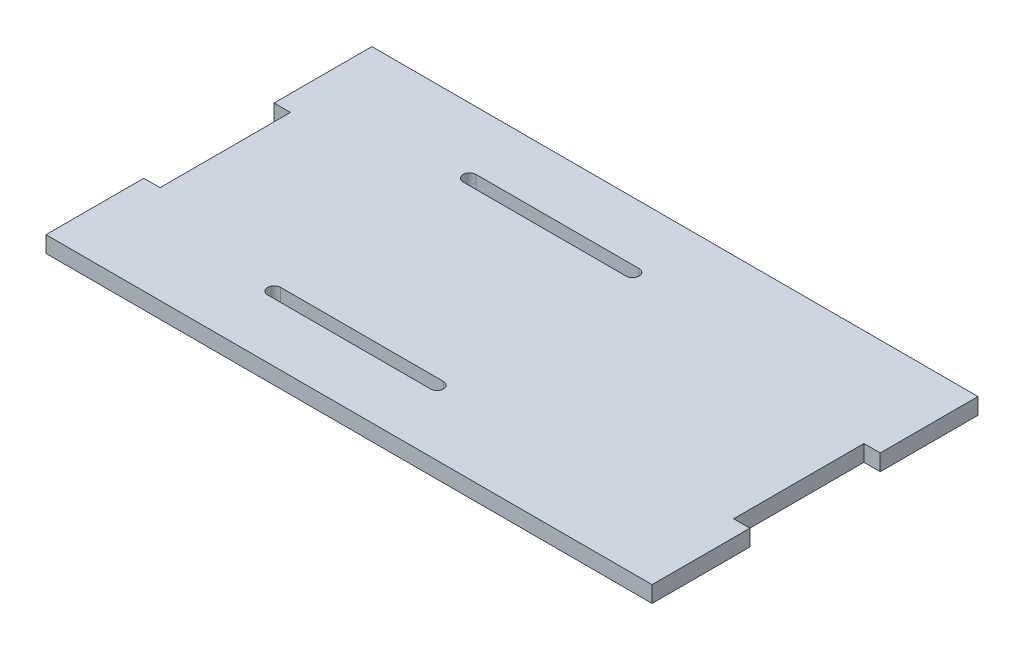
SolidWorks part; units mm, degrees
ref_plane "Front" through (0, 0, 0) normal (0, 0, 1) x (1, 0, 0)
ref_plane "Top" through (0, 0, 0) normal (0, 1, 0) x (1, 0, 0)
ref_plane "Right" through (0, 0, 0) normal (1, 0, 0) x (0, 0, -1)
sketch "Skizze1" plane through (0, 0, 0) normal (0, 1, 0) x (1, 0, 0)
  line L1 (0, 0) -> (186, 0)
  line L2 (0, 0) -> (0, 100)
  line L3 (0, 100) -> (186, 100)
  line L4 (186, 0) -> (186, 100)
  dimension "D1" = 100
  dimension "D2" = 186
extrude "Aufsatz-Linear austragen1" add sketch "Skizze1" along normal blind 5
sketch "Skizze2" plane through (0, 5, 0) normal (0, 1, 0) x (1, 0, 0)
  line L0 (186, 50) -> (93, 50) construction
  line L1 (186, 0) -> (186, 100) construction
  line L2 (93, 50) -> (93, 0) construction
  line L3 (0, 0) -> (186, 0) construction
  line L4 (186, 70) -> (186, 30)
  line L5 (186, 30) -> (181, 30)
  line L6 (181, 30) -> (181, 70)
  line L7 (186, 70) -> (181, 70)
  line L8 (0, 70) -> (5, 70)
  line L9 (5, 30) -> (5, 70)
  line L10 (0, 30) -> (5, 30)
  line L11 (0, 70) -> (0, 30)
  point P11 (181, 50)
  point P16 (5, 50)
  dimension "D1" = 5
  dimension "D2" = 40
extrude "Schnitt-Linear austragen1" cut sketch "Skizze2" against normal through all
sketch "Skizze3" [suppressed] plane through (0, 5, 0) normal (0, 1, 0) x (1, 0, 0)
  line L0 (0, 0) -> (120, 0) construction
  line L1 (90, 0) -> (0, 0)
  line L2 (90, 0) -> (90, 65)
  line L3 (90, 65) -> (0, 65)
  line L4 (0, 0) -> (0, 65)
  line L5 (120, 0) -> (120, 12.5) construction
  dimension "D1" = 30
extrude "Schnitt-Linear austragen2" [suppressed] cut sketch "Skizze3" against normal through all
sketch "Skizze4" plane through (0, 5, 0) normal (0, 1, 0) x (1, 0, 0)
  line L0 (5, 50) -> (75, 50) construction
  line L1 (5, 30) -> (5, 70) construction
  line L2 (75, 50) -> (75, 80) construction
  line L3 (100, 80) -> (50, 80) construction
  line L4 (100, 78) -> (50, 78)
  line L5 (100, 82) -> (50, 82)
  line L6 (100, 20) -> (50, 20) construction
  line L7 (100, 22) -> (50, 22)
  line L8 (100, 18) -> (50, 18)
  arc A0 (100, 78) -> (100, 82) centre (100, 80) ccw
  arc A1 (50, 82) -> (50, 78) centre (50, 80) ccw
  arc A2 (100, 22) -> (100, 18) centre (100, 20) cw
  arc A3 (50, 18) -> (50, 22) centre (50, 20) cw
  point P7 (75, 80)
  point P14 (75, 20)
  dimension "D1" = 2
  dimension "D2" = 50
  dimension "D3" = 70
  dimension "D4" = 60
extrude "Schnitt-Linear austragen3" cut sketch "Skizze4" against normal through all
